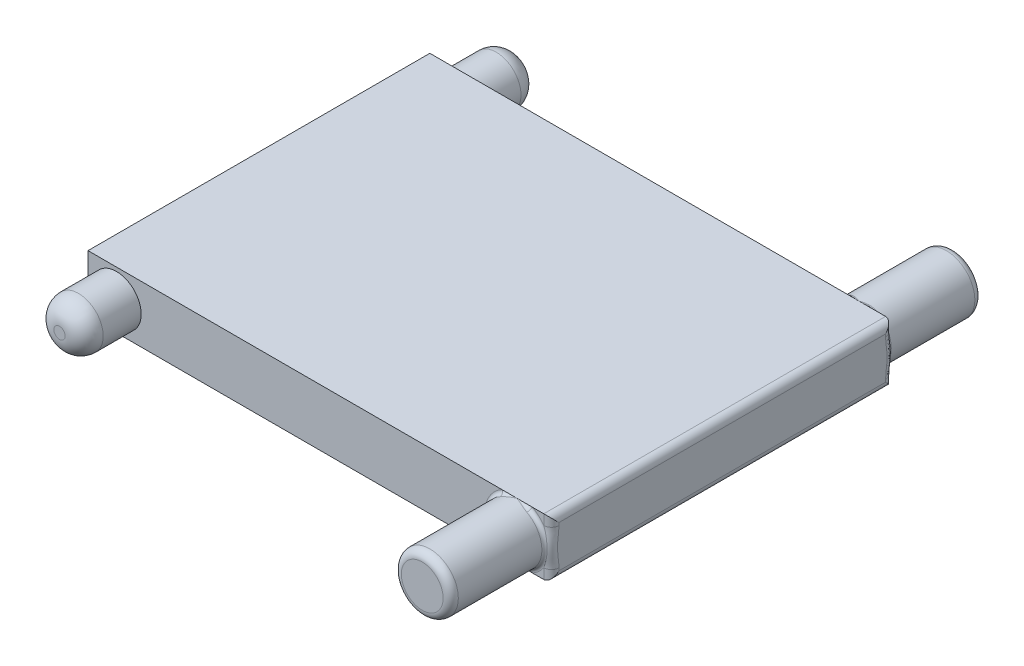
SolidWorks part; units mm, degrees
ref_plane "Front Plane" through (0, 0, 0) normal (0, 0, 1) x (1, 0, 0)
ref_plane "Top Plane" through (0, 0, 0) normal (0, 1, 0) x (1, 0, 0)
ref_plane "Right Plane" through (0, 0, 0) normal (1, 0, 0) x (0, 0, -1)
sketch "Sketch1" plane through (0, 0, 0) normal (0, 1, 0) x (1, 0, 0)
  line L1 (0, 0) -> (12.2, 0)
  line L2 (0, 0) -> (0, 9)
  line L3 (0, 9) -> (12.2, 9)
  line L4 (12.2, 0) -> (12.2, 9)
  dimension "D1" = 12.2
  dimension "D2" = 9
extrude "Boss-Extrude1" add sketch "Sketch1" along normal blind 1.5
sketch "Sketch2" plane through (0, 0, 0) normal (0, 0, 1) x (1, 0, 0)
  line L0 (0, 1.5) -> (0, 0) construction
  line L1 (0, 0) -> (12.2, 0) construction
  circle A0 centre (0.75, 0.75) radius 0.65
  dimension "D1" = 1.3
  dimension "D2" = 0.75
  dimension "D3" = 0.75
extrude "Boss-Extrude2" add sketch "Sketch2" along normal blind 1.5 and the other way blind 10.5 contours A0
fillet "Fillet1" radius 0.5 1 edges at (1.4, 0.75, 1.5)
fillet "Fillet3" radius 0.5 1 edges at (1.4, 0.75, -10.5)
sketch "Sketch3" plane through (0, 0, 0) normal (0, 0, 1) x (1, 0, 0)
  line L0 (0, 0) -> (12.2, 0) construction
  line L1 (12.2, 1.5) -> (12.2, 0) construction
  circle A0 centre (11.3, 0.75) radius 0.75
  dimension "D1" = 1.5
  dimension "D2" = 0.75
  dimension "D3" = 0.9
extrude "Boss-Extrude3" add sketch "Sketch3" along normal blind 2.5 and the other way blind 11.5
fillet "Fillet4" radius 0.1 2 edges at (12.05, 0.75, 0) (10.55, 0.75, 0)
fillet "Fillet5" radius 0.1 2 edges at (10.55, 0.75, -9) (12.05, 0.75, -9)
fillet "Fillet6" radius 0.2 2 edges at (12.05, 0.75, -11.5) (12.05, 0.75, 2.5)
fillet "Fillet7" radius 0.2 4 edges at (12.2, 0.75, 0) (12.2, 1.5, -4.5) (12.2, 0.75, -9) (12.2, 0, -4.5)
